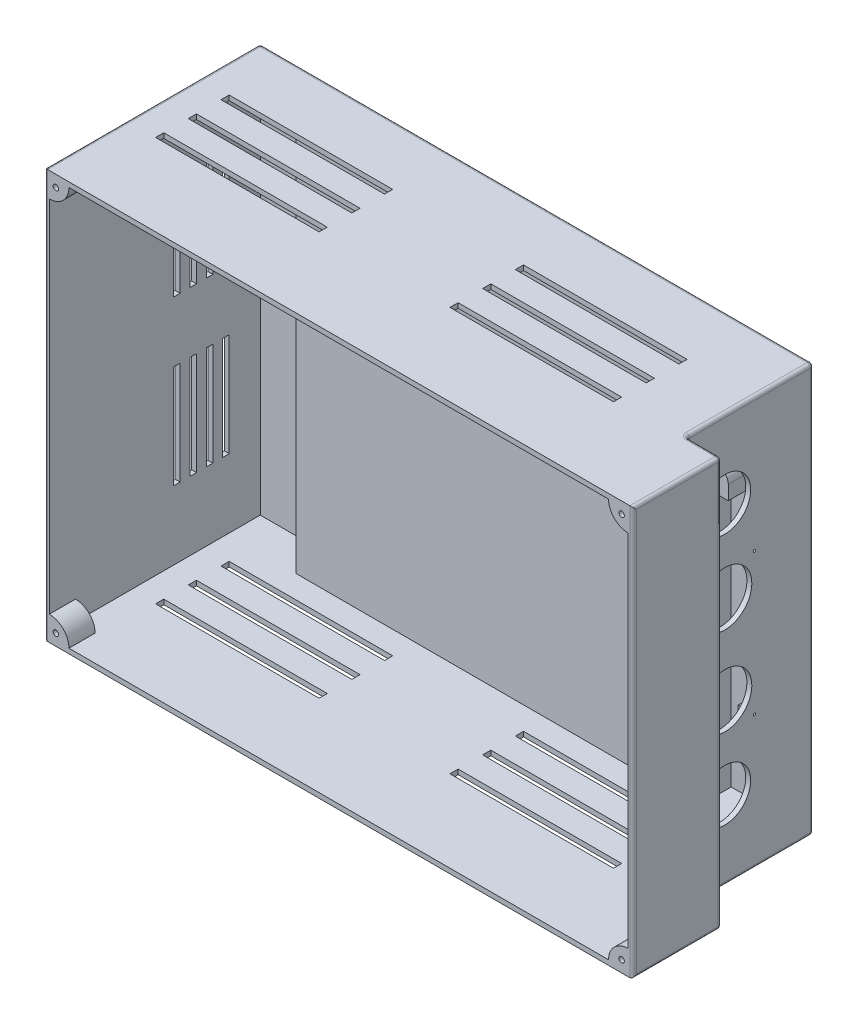
SolidWorks part; units mm, degrees
ref_plane "前视基准面" through (0, 0, 0) normal (0, 0, 1) x (1, 0, 0)
ref_plane "上视基准面" through (0, 0, 0) normal (0, 1, 0) x (1, 0, 0)
ref_plane "右视基准面" through (0, 0, 0) normal (1, 0, 0) x (0, 0, -1)
sketch "草图2" plane through (0, 0, 0) normal (0, 0, 1) x (1, 0, 0)
  line L1 (-90, 62.5) -> (90, 62.5)
  line L2 (-90, 62.5) -> (-90, -62.5)
  line L3 (-90, -62.5) -> (90, -62.5)
  line L4 (90, 62.5) -> (90, -62.5)
  line L5 (-90, 62.5) -> (90, -62.5) construction
  line L6 (-90, -62.5) -> (90, 62.5) construction
  point P0 (0, 0)
  dimension "D1" = 180
  dimension "D2" = 125
extrude "凸台-拉伸1" add sketch "草图2" along normal blind 66
sketch "草图3" plane through (0, 0, 0) normal (0, 0, -1) x (-1, 0, 0)
  line L0 (66, 59.5) -> (66, -59.5)
  line L1 (66, -59.5) -> (-54, -59.5)
  line L3 (66, 59.5) -> (-54, 59.5)
  line L4 (-54, -59.5) -> (-54, 59.5)
  line L5 (-90, 62.5) -> (90, 62.5) construction
  line L7 (90, -62.5) -> (-90, -62.5) construction
  line L9 (-90, -62.5) -> (-90, 62.5) construction
  line L11 (90, 62.5) -> (90, -62.5) construction
  dimension "D1" = 3
  dimension "D2" = 24
  dimension "D3" = 3
  dimension "D4" = 36
extrude "切除-拉伸1" cut sketch "草图3" against normal blind 10
sketch "草图4" plane through (90, 0, 0) normal (1, 0, 0) x (0, 0, -1)
  line L0 (-39, -62.5) -> (-39, 62.5)
  line L1 (-66, 61.5) -> (-66, -61.5) construction
  line L2 (-66, 62.5) -> (0, 62.5) construction
  line L4 (0, -62.5) -> (0, 62.5)
  line L6 (-66, 62.5) -> (-66, -62.5)
  line L9 (0, 62.5) -> (-39, 62.5)
  line L11 (-39, -62.5) -> (0, -62.5)
  line L14 (0, -62.5) -> (0, 62.5)
  line L15 (0, 62.5) -> (-66, 62.5)
  line L16 (-66, -62.5) -> (0, -62.5)
  dimension "D2" = 27
  dimension "D1" = 0
extrude "切除-拉伸2" cut sketch "草图4" against normal offset from surface (10.8 mm away) 2
shell "抽壳1" thickness 1.5 removed face at (0, 0, 66)
sketch "草图6" plane through (79.2, 0, 0) normal (1, 0, 0) x (0, 0, -1)
  line L1 (-16.0647, -23.6651) -> (-20.0647, -23.6651)
  line L2 (-16.0647, -23.6651) -> (-16.0647, -19.6651)
  line L3 (-16.0647, -19.6651) -> (-20.0647, -19.6651)
  line L4 (-20.0647, -23.6651) -> (-20.0647, -19.6651)
  line L5 (-34.2212, -23.6651) -> (-38.2212, -23.6651)
  line L6 (-34.2212, -23.6651) -> (-34.2212, -19.6651)
  line L7 (-34.2212, -19.6651) -> (-38.2212, -19.6651)
  line L8 (-38.2212, -23.6651) -> (-38.2212, -19.6651)
  line L9 (-34.2212, 19.6651) -> (-38.2212, 19.6651)
  line L10 (-34.2212, 19.6651) -> (-34.2212, 23.6651)
  line L11 (-34.2212, 23.6651) -> (-38.2212, 23.6651)
  line L12 (-38.2212, 19.6651) -> (-38.2212, 23.6651)
  line L13 (-16.0647, 19.6651) -> (-20.0647, 19.6651)
  line L14 (-16.0647, 19.6651) -> (-16.0647, 23.6651)
  line L15 (-16.0647, 23.6651) -> (-20.0647, 23.6651)
  line L16 (-20.0647, 19.6651) -> (-20.0647, 23.6651)
  arc A0 (-18.5647, 21.6651) -> (-17.5647, 21.6651) centre (-18.0647, 21.6651) ccw construction
  arc A1 (-17.5647, 21.6651) -> (-18.5647, 21.6651) centre (-18.0647, 21.6651) ccw construction
  arc A2 (-35.7212, 21.6651) -> (-36.7212, 21.6651) centre (-36.2212, 21.6651) ccw construction
  arc A3 (-36.7212, 21.6651) -> (-35.7212, 21.6651) centre (-36.2212, 21.6651) ccw construction
  arc A4 (-36.7212, -21.6651) -> (-35.7212, -21.6651) centre (-36.2212, -21.6651) ccw construction
  arc A5 (-18.5647, -21.6651) -> (-17.5647, -21.6651) centre (-18.0647, -21.6651) ccw construction
  dimension "D10" = 2
  dimension "D1" = 2
  dimension "D2" = 2
  dimension "D3" = 2
  dimension "D4" = 2
  dimension "D5" = 4
  dimension "D6" = 2
  dimension "D7" = 4
  dimension "D8" = 2
  dimension "D9" = 2
  dimension "D11" = 4
  dimension "D12" = 4
  dimension "D13" = 2
  dimension "D14" = 2
  dimension "D15" = 4
  dimension "D16" = 4
extrude "凸台-拉伸2" add sketch "草图6" against normal up to surface (3 mm away)
sketch "草图7" plane through (79.2, 0, 0) normal (1, 0, 0) x (0, 0, -1)
  circle A0 centre (-27.143, -13.5) radius 8.25
  circle A1 centre (-27.143, 13.5) radius 8.25
  circle A2 centre (-18.0647, -21.6651) radius 0.375
  circle A3 centre (-18.0647, 21.6651) radius 0.375
  circle A4 centre (-36.2212, 21.6651) radius 0.375
  circle A5 centre (-36.2212, -21.6651) radius 0.375
  arc A6 (-19.143, -13.5) -> (-35.143, -13.5) centre (-27.143, -13.5) ccw construction
  circle A7 centre (-27.143, 38.5) radius 7.9
  circle A8 centre (-27.143, 38.5) radius 7.65 construction
  circle A9 centre (-27.143, -38.5) radius 7.9
  dimension "D1" = 0.75
  dimension "D2" = 0.25
  dimension "D3" = 0.25
extrude "切除-拉伸3" cut sketch "草图7" against normal up to next
sketch "草图8" plane through (0, -62.5, 0) normal (0, -1, 0) x (1, 0, 0)
  line L0 (-90, 66) -> (90, 66) construction
  line L1 (-81, 41) -> (-31, 41)
  line L2 (-81, 41) -> (-81, 38.5)
  line L3 (-81, 38.5) -> (-31, 38.5)
  line L4 (-31, 41) -> (-31, 38.5)
  line L5 (-90, 66) -> (-90, 0) construction
  line L6 (9, 41) -> (59, 41)
  line L7 (9, 41) -> (9, 38.5)
  line L8 (9, 38.5) -> (59, 38.5)
  line L9 (59, 41) -> (59, 38.5)
  line L10 (9, 31) -> (59, 31)
  line L11 (9, 31) -> (9, 28.5)
  line L12 (9, 28.5) -> (59, 28.5)
  line L13 (59, 31) -> (59, 28.5)
  line L14 (9, 21) -> (59, 21)
  line L15 (9, 21) -> (9, 18.5)
  line L16 (9, 18.5) -> (59, 18.5)
  line L17 (59, 21) -> (59, 18.5)
  line L18 (-81, 31) -> (-31, 31)
  line L19 (-81, 31) -> (-81, 28.5)
  line L20 (-81, 28.5) -> (-31, 28.5)
  line L21 (-31, 31) -> (-31, 28.5)
  line L22 (-81, 21) -> (-31, 21)
  line L23 (-81, 21) -> (-81, 18.5)
  line L24 (-81, 18.5) -> (-31, 18.5)
  line L25 (-31, 21) -> (-31, 18.5)
  dimension "D1" = 2.5
  dimension "D2" = 25
  dimension "D3" = 9
  dimension "D4" = 50
  dimension "D5" = 2
  dimension "D6" = 3
extrude "切除-拉伸4" cut sketch "草图8" against normal up to surface (125 mm away) and the other way through all up to face at (26.4, 62.5, 35)
sketch "草图9" plane through (0, 0, 66) normal (0, 0, 1) x (1, 0, 0)
  line L1 (-88.5, 61) -> (-82.5, 61)
  line L2 (-88.5, 61) -> (-88.5, 55)
  line L5 (0, 0) -> (0, 36.715) construction
  line L6 (0, 0) -> (38.7304, 0) construction
  line L7 (-88.5, -61) -> (-88.5, -55)
  line L8 (-88.5, -61) -> (-82.5, -61)
  line L9 (88.5, -61) -> (82.5, -61)
  line L10 (88.5, -61) -> (88.5, -55)
  line L11 (88.5, 61) -> (88.5, 55)
  line L12 (88.5, 61) -> (82.5, 61)
  circle A0 centre (-86.5, 59) radius 0.825
  arc A1 (-82.5, 61) -> (-88.5, 55) centre (-88.5, 61) cw
  arc A2 (-82.5, -61) -> (-88.5, -55) centre (-88.5, -61) ccw
  circle A3 centre (-86.5, -59) radius 0.825
  circle A4 centre (86.5, -59) radius 0.825
  arc A5 (82.5, -61) -> (88.5, -55) centre (88.5, -61) cw
  arc A6 (82.5, 61) -> (88.5, 55) centre (88.5, 61) ccw
  circle A7 centre (86.5, 59) radius 0.825
  dimension "D1" = 1.65
  dimension "D2" = 2
  dimension "D3" = 2
  dimension "D4" = 6
extrude "凸台-拉伸3" add sketch "草图9" against normal blind 8
sketch "草图10" plane through (0, 0, 1.5) normal (0, 0, 1) x (1, 0, 0)
  line L0 (77.7, -61) -> (77.7, 61) construction
  line L1 (77.7, 50.5757) -> (70.499, 50.5757)
  line L2 (77.7, 50.5757) -> (77.7, 61)
  line L3 (77.7, 61) -> (70.499, 61)
  line L4 (70.499, 50.5757) -> (70.499, 61)
  line L5 (82.5, 61) -> (-82.5, 61) construction
  line L6 (55.5, 61) -> (55.5, -61) construction
  line L7 (62.513, 50.5757) -> (55.5, 50.5757)
  line L8 (62.513, 50.5757) -> (62.513, 61)
  line L9 (62.513, 61) -> (55.5, 61)
  line L10 (55.5, 50.5757) -> (55.5, 61)
  line L11 (62.513, 22.2546) -> (55.5, 22.2546)
  line L12 (62.513, 22.2546) -> (62.513, 29.6276)
  line L13 (62.513, 29.6276) -> (55.5, 29.6276)
  line L14 (55.5, 22.2546) -> (55.5, 29.6276)
  line L16 (77.7, 22.2546) -> (70.499, 22.2546)
  line L17 (77.7, 22.2546) -> (77.7, 29.6276)
  line L18 (77.7, 29.6276) -> (70.499, 29.6276)
  line L19 (70.499, 22.2546) -> (70.499, 29.6276)
  arc A0 (73.999, 27.2546) -> (73.999, 25.2546) centre (73.999, 26.2546) ccw construction
  arc A1 (59.013, 25.1276) -> (59.013, 27.1276) centre (59.013, 26.1276) ccw construction
  arc A2 (59.013, 27.1276) -> (59.013, 25.1276) centre (59.013, 26.1276) ccw construction
  arc A4 (74.126, 53.5757) -> (74.126, 55.5757) centre (74.126, 54.5757) ccw construction
  circle A5 centre (74.126, 54.5757) radius 0.825
  circle A6 centre (59.14, 54.5757) radius 0.825
  circle A7 centre (59.013, 26.1276) radius 0.825
  circle A8 centre (73.999, 26.2546) radius 0.825
  dimension "D7" = 1.65
  dimension "D6" = 1.65
  dimension "D8" = 1.65
  dimension "D9" = 1.65
  dimension "D1" = 4
  dimension "D2" = 3.5
  dimension "D3" = 3.5
  dimension "D4" = 3.5
  dimension "D5" = 4
extrude "开关螺孔凸台-拉伸4" add sketch "草图10" along normal up to surface (7.8999 mm away)
sketch "草图11" plane through (0, 0, 0) normal (0, 0, -1) x (-1, 0, 0)
  circle A0 centre (-66.76, 36.1607) radius 6.1
  circle A5 centre (-65.482, 49.2417) radius 2.6
  dimension "D1" = 12.2
  dimension "D2" = 5.2
extrude "切除-拉伸5" cut sketch "草图11" against normal up to next
fillet "圆角1" radius 3 4 edges at (62.513, 29.6276, 5.45) (62.513, 50.5757, 5.45) (70.499, 29.6276, 5.45) (70.499, 50.5757, 5.45)
fillet "圆角2" radius 1 26 edges at (90, 0, 66) (90, 0, 39) (79.2, 0, 39) (-90, 0, 66) (-90, -62.5, 33) (90, -62.5, 52.5) (84.6, -62.5, 39) (79.2, -62.5, 19.5) (-90, 62.5, 33) (79.2, 62.5, 19.5) (84.6, 62.5, 39) (90, 62.5, 52.5) (-5.4, 62.5, 0) (-90, 0, 0) (-5.4, -62.5, 0) (79.2, 0, 0) (-66, 0, 0) (-6, 59.5, 0) (54, 0, 0) (-6, -59.5, 0) (62.882, 49.2417, 0) (60.66, 36.1607, 0) (-6, 59.5, 10) (-66, 0, 10) (-6, -59.5, 10) (54, 0, 10)
sketch "草图12" plane through (-90, 0, 0) normal (-1, 0, 0) x (0, 0, 1)
  line L0 (1, 61.5) -> (1, -61.5) construction
  line L1 (11, 41.5) -> (13, 41.5)
  line L2 (11, 41.5) -> (11, 10)
  line L3 (11, 10) -> (13, 10)
  line L4 (13, 41.5) -> (13, 10)
  line L5 (65, 61.5) -> (1, 61.5) construction
  line L6 (16, 41.5) -> (18, 41.5)
  line L7 (16, 41.5) -> (16, 10)
  line L8 (16, 10) -> (18, 10)
  line L9 (18, 41.5) -> (18, 10)
  line L10 (21, 41.5) -> (23, 41.5)
  line L11 (21, 41.5) -> (21, 10)
  line L12 (21, 10) -> (23, 10)
  line L13 (23, 41.5) -> (23, 10)
  line L14 (26, 41.5) -> (28, 41.5)
  line L15 (26, 41.5) -> (26, 10)
  line L16 (26, 10) -> (28, 10)
  line L17 (28, 41.5) -> (28, 10)
  line L18 (16, -8.5) -> (18, -8.5)
  line L19 (16, -8.5) -> (16, -40)
  line L20 (16, -40) -> (18, -40)
  line L21 (18, -8.5) -> (18, -40)
  line L22 (21, -8.5) -> (23, -8.5)
  line L23 (21, -8.5) -> (21, -40)
  line L24 (21, -40) -> (23, -40)
  line L25 (23, -8.5) -> (23, -40)
  line L26 (26, -8.5) -> (28, -8.5)
  line L27 (26, -8.5) -> (26, -40)
  line L28 (26, -40) -> (28, -40)
  line L29 (28, -8.5) -> (28, -40)
  line L30 (11, -8.5) -> (13, -8.5)
  line L31 (11, -8.5) -> (11, -40)
  line L32 (11, -40) -> (13, -40)
  line L33 (13, -8.5) -> (13, -40)
  dimension "D1" = 2
  dimension "D2" = 31.5
  dimension "D3" = 10
  dimension "D4" = 20
  dimension "D5" = 4
  dimension "D6" = 2
extrude "切除-拉伸6" cut sketch "草图12" against normal up to next
